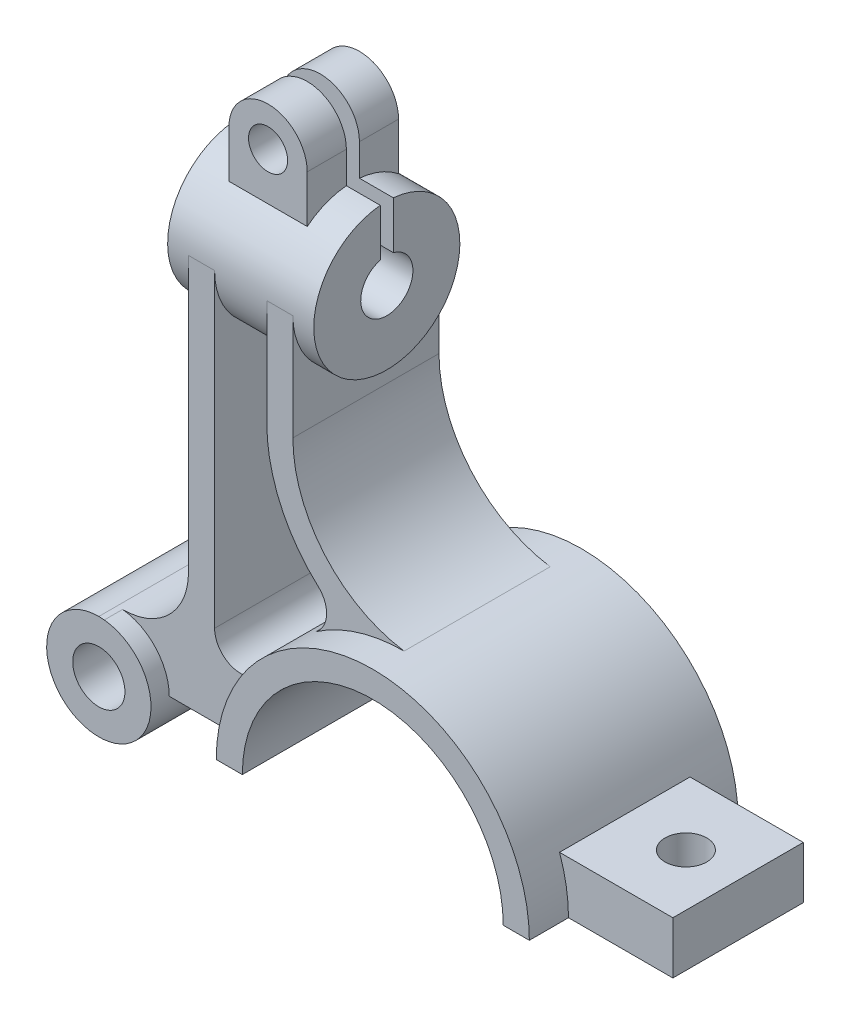
SolidWorks part; units mm, degrees
ref_plane "Front Plane" through (0, 0, 0) normal (0, 0, 1) x (1, 0, 0)
ref_plane "Top Plane" through (0, 0, 0) normal (0, 1, 0) x (1, 0, 0)
ref_plane "Right Plane" through (0, 0, 0) normal (1, 0, 0) x (0, 0, -1)
sketch "Sketch1" plane through (0, 0, 0) normal (0, 0, 1) x (1, 0, 0)
  line L0 (-131.6592, 0) -> (287.0487, 0) construction
  line L1 (-60, 0) -> (-50, 0)
  line L2 (50, 0) -> (60, 0)
  line L3 (60, 0) -> (100, 0)
  line L4 (100, 0) -> (100, 20)
  line L5 (100, 20) -> (56.5685, 20)
  line L6 (-60, 0) -> (-90, 0)
  line L7 (0, -47.5624) -> (0, 82.9916) construction
  line L8 (-110, -33.9413) -> (-110, 52.5167) construction
  line L9 (-52.6303, 140) -> (-52.6303, 109.4539)
  line L10 (-82.6303, 150) -> (-42.6303, 150)
  line L11 (-82.6303, 150) -> (-82.6303, 44.8874)
  line L13 (-42.6303, 150) -> (-42.6303, 109.4539)
  line L15 (-72.6303, 140) -> (-72.6303, 31.2642)
  line L16 (-72.6303, 140) -> (-72.6303, 44.8874) construction
  line L17 (-72.6303, 140) -> (-52.6303, 140) construction
  line L18 (-72.6303, 140) -> (-72.6303, 150)
  line L19 (-52.6303, 140) -> (-52.6303, 150)
  circle A0 centre (-110, 0) radius 20
  circle A1 centre (-110, 0) radius 10
  arc A2 (60, 0) -> (-60, 0) centre (0, 0) ccw
  arc A3 (50, 0) -> (-50, 0) centre (0, 0) ccw
  arc A4 (-110, 20) -> (-82.6303, 44.8874) centre (-107.6303, 44.8874) ccw
  arc A5 (0, 60) -> (-42.6303, 109.4539) centre (7.3697, 109.4539) cw
  arc A6 (-32.9817, 65.0494) -> (-34.0345, 49.4131) centre (-39.7069, 57.6486) cw
  arc A7 (-32.9817, 65.0494) -> (-52.6303, 109.4539) centre (7.3697, 109.4539) cw
  arc A8 (-53.6831, 26.7979) -> (-34.0345, 49.4131) centre (0, 0) cw
  arc A9 (-110.9479, 10.045) -> (-72.6303, 44.8874) centre (-107.6303, 44.8874) ccw construction
  arc A10 (-1.4739, 50.1092) -> (-52.6303, 109.4539) centre (7.3697, 109.4539) cw construction
  arc A11 (-53.6831, 26.7979) -> (-72.6303, 31.2642) centre (-62.6303, 31.2642) cw
  point P23 (-62.6303, 150)
  point P34 (0, 0)
  point P37 (0, 0)
  dimension "D1" = 20
  dimension "D2" = 40
  dimension "D3" = 120
  dimension "D4" = 100
  dimension "D10" = 25
  dimension "D11" = 50
  dimension "D13" = 10
  dimension "D5" = 110
  dimension "D6" = 20
  dimension "D7" = 100
  dimension "D8" = 40
  dimension "D9" = 150
  dimension "D14" = 82.6303
  dimension "D12" = 10
extrude "Boss-Extrude1" add sketch "Sketch1" along normal mid plane 80 contours A3 L2 A2 L1 region at (-57.0936, 13.4584, 0)
extrude "Boss-Extrude2" add sketch "Sketch1<3>" along normal mid plane 70 separate body contours A4 A0 A1 region at (-123.7421, -13.7421, 0)
sketch "Sketch1<3>" plane through (0, 0, 0) normal (0, 0, 1) x (1, 0, 0) same geometry as "Sketch1"
extrude "Boss-Extrude3" add sketch "Sketch1<6>" along normal mid plane 56 contours A7 A6 A2 A5 L13 L10 L19 L9 | A2 A11 L15 L18 L10 L11 A4 A0 L6 region at (-77.7401, 56.0214, 0) region at (-28.5968, 56.9005, 0)
sketch "Sketch1<6>" plane through (0, 0, 0) normal (0, 0, 1) x (1, 0, 0) same geometry as "Sketch1"
extrude "Boss-Extrude4" add sketch "Sketch1<7>" along normal mid plane 50 contours A2 L3 L4 L5 region at (79.4222, 10.1382, 0)
sketch "Sketch1<7>" plane through (0, 0, 0) normal (0, 0, 1) x (1, 0, 0) same geometry as "Sketch1"
sketch "Sketch3" plane through (0, 20, 0) normal (0, 1, 0) x (1, 0, 0)
  line L0 (100, 25) -> (56.5685, 25) construction
  circle A0 centre (80, 0) radius 8
  dimension "D1" = 16
  dimension "D2" = 80
  dimension "D3" = 25
extrude "Cut-Extrude1" cut sketch "Sketch3" against normal blind 67
ref_plane "Plane1" through (-62.6303, 0, 0) normal (1, 0, 0) x (0, 0, -1)
sketch "Sketch8" plane through (-62.6303, 0, 0) normal (1, 0, 0) x (0, 0, -1)
  line L0 (0, 176.6164) -> (0, 132.7421) construction
  line L1 (-28, 150) -> (28, 150) construction
  circle A0 centre (0, 150) radius 28
  dimension "D1" = 56
extrude "Boss-Extrude5" add sketch "Sketch8" along normal mid plane 56
sketch "Sketch9" plane through (0, 0, 0) normal (0, 0, 1) x (1, 0, 0)
  line L0 (-52.6303, 150) -> (-42.6303, 150) construction
  line L2 (-77.6303, 190) -> (-77.6303, 170)
  line L3 (-77.6303, 170) -> (-47.6303, 170)
  line L4 (-47.6303, 190) -> (-47.6303, 170)
  arc A0 (-77.6303, 190) -> (-47.6303, 190) centre (-62.6303, 190) cw
  circle A1 centre (-62.6303, 190) radius 7.5
  point P6 (-62.6303, 170)
  dimension "D1" = 15
  dimension "D2" = 15
  dimension "D3" = 20
  dimension "D4" = 40
extrude "Boss-Extrude6" add sketch "Sketch9" along normal mid plane 35
sketch "Sketch10" plane through (-34.6303, 0, 0) normal (1, 0, 0) x (0, 0, -1)
  line L0 (17.5, 205) -> (-17.5, 205) construction
  line L1 (-2.5, 150) -> (2.5, 150)
  line L2 (-2.5, 150) -> (-2.5, 205)
  line L3 (-2.5, 205) -> (2.5, 205)
  line L4 (2.5, 150) -> (2.5, 205)
  circle A0 centre (0, 150) radius 10
  circle M4 centre (0, 150) radius 28
  dimension "D1" = 20
  dimension "D2" = 2.5
  dimension "D3" = 5
extrude "Cut-Extrude3" cut sketch "Sketch10" against normal blind 60 contours A0
extrude "Cut-Extrude4" cut sketch "Sketch10<4>" against normal blind 60 contours A0 L4 L2 M4 | L4 L3 L2 M4 region at (-34.6303, 168.9286, 0) region at (-34.6303, 191.4814, 0)
sketch "Sketch10<4>" plane through (-34.6303, 0, 0) normal (1, 0, 0) x (0, 0, -1) same geometry as "Sketch10"
